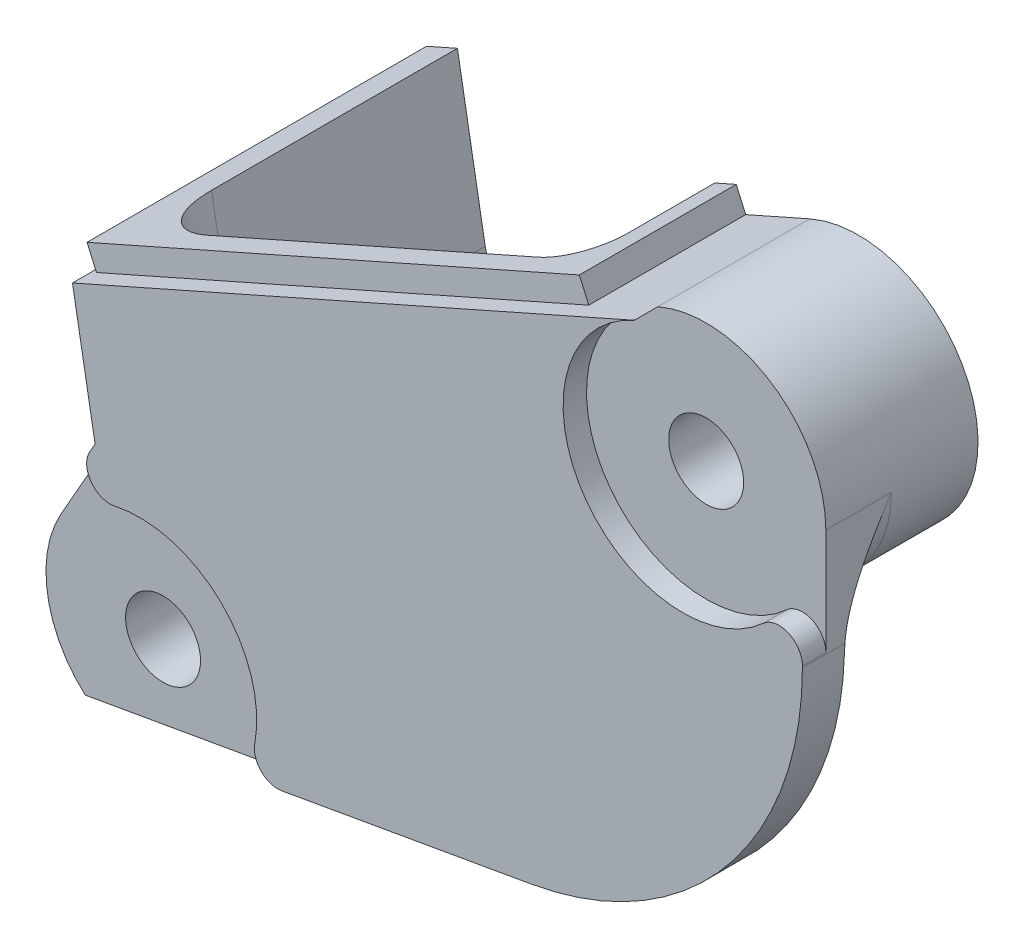
SolidWorks part; units mm, degrees
ref_plane "前视基准面" through (0, 0, 0) normal (0, 0, 1) x (1, 0, 0)
ref_plane "上视基准面" through (0, 0, 0) normal (0, 1, 0) x (1, 0, 0)
ref_plane "右视基准面" through (0, 0, 0) normal (1, 0, 0) x (0, 0, -1)
other "Configuration Table"
sketch "草图1" plane through (0, 0, 0) normal (0, 0, 1) x (1, 0, 0)
  line L0 (-7.0476, 5.9136) -> (0, 5.9136) construction
  line L1 (0, 5.9136) -> (0, 0) construction
  line L2 (0, 0) -> (-7.0476, 5.9136) construction
  line L3 (-12.4776, 6.0041) -> (2.6676, 12.706)
  line L4 (2.6676, 12.706) -> (2.6676, -8.6685)
  line L5 (-12.4776, 6.0041) -> (-12.4776, -11.339)
  line L6 (-12.4776, -11.339) -> (2.6676, -8.6685)
  circle A0 centre (0, 0) radius 1
  circle A1 centre (-7.0476, 5.9136) radius 1
  dimension "D1" = 9.2
  dimension "D3" = 2
  dimension "D4" = 2
  dimension "D9" = 5.43
  dimension "D8" = 9
  dimension "D2" = 50
  dimension "D5" = 2.28
  dimension "D6" = 63.87
  dimension "D7" = 2.6676
  dimension "D10" = 50
extrude "凸台-拉伸1" add sketch "草图1" along normal blind 1.4
sketch "草图2" plane through (0, 0, 0) normal (0, 0, -1) x (-1, 0, 0)
  circle A0 centre (7.0476, 5.9136) radius 2
  circle A1 centre (7.0476, 5.9136) radius 1 construction
  circle A2 centre (7.0476, 5.9136) radius 1
  dimension "D1" = 4
extrude "凸台-拉伸2" add sketch "草图2" along normal blind 1
sketch "草图3" plane through (0, 0, 0) normal (0, 0, -1) x (-1, 0, 0)
  circle A0 centre (0, 0) radius 2
  circle A1 centre (0, 0) radius 1 construction
  circle A2 centre (0, 0) radius 1
  circle A4 centre (7.0476, 5.9136) radius 2 construction
extrude "凸台-拉伸3" add sketch "草图3" along normal blind 0.4
sketch "草图4" plane through (0, 0, 1.4) normal (0, 0, 1) x (1, 0, 0)
  circle A0 centre (-7.0476, 5.9136) radius 1 construction
  circle A1 centre (-7.0476, 5.9136) radius 1
extrude "凸台-拉伸4" add sketch "草图4" against normal blind 1
sketch "草图5" plane through (0, 0, 1.4) normal (0, 0, 1) x (1, 0, 0)
  line L0 (0, 0) -> (8.1261, 1.4328) construction
  line L1 (8.1261, 1.4328) -> (8.1261, 9.5328) construction
  line L2 (-12.4776, -11.339) -> (2.6676, -8.6685) construction
  line L5 (2.6676, 12.706) -> (2.6676, -8.6685)
  line L6 (2.6676, -8.6685) -> (13.2367, -6.8049)
  line L7 (13.2367, -6.8049) -> (13.2367, 9.5328)
  line L8 (-12.4776, -11.339) -> (-14.5289, -11.7007) construction
  line L9 (-14.5289, -11.7007) -> (-15.0672, -8.6478) construction
  line L10 (0, 0) -> (1.5628, -8.8633) construction
  line L11 (-12.4776, -11.339) -> (-18.3923, -12.3819)
  line L12 (-12.4776, 6.0041) -> (-19.4121, -6.1736)
  line L13 (-12.4776, 6.0041) -> (-12.4776, -11.339)
  line L14 (2.6676, 12.706) -> (6.058, 14.2063)
  line L15 (2.6676, 12.706) -> (-12.4776, 6.0041) construction
  line L16 (8.1261, 9.5328) -> (9.5113, 1.6771) construction
  line L17 (9.5113, 1.6771) -> (8.1261, 1.4328) construction
  arc A0 (13.2367, 9.5328) -> (6.058, 14.2063) centre (8.1261, 9.5328) ccw
  arc A4 (-19.4121, -6.1736) -> (-18.3923, -12.3819) centre (-15.0672, -8.6478) ccw
  dimension "D1" = 8.1
  dimension "D2" = 9.658
  dimension "D3" = 16.34
  dimension "D5" = 5
  dimension "D4" = 3.1
extrude "凸台-拉伸5" add sketch "草图5" against normal up to surface (1.4 mm away) up to face at (-5.0476, 5.9136, 0)
sketch "草图6" plane through (0, 0, 1.4) normal (0, 0, 1) x (1, 0, 0)
  line L4 (6.058, 14.2063) -> (-12.4776, 6.0041)
  line L5 (-12.4776, 6.0041) -> (-19.4121, -6.1736)
  line L6 (-18.3923, -12.3819) -> (13.2367, -6.8049)
  line L7 (13.2367, -6.8049) -> (13.2367, 9.5328)
  line L8 (6.058, 14.2063) -> (-12.4776, 6.0041)
  line L9 (-12.4776, 6.0041) -> (-19.4121, -6.1736)
  line L10 (-18.3923, -12.3819) -> (13.2367, -6.8049)
  line L11 (13.2367, -6.8049) -> (13.2367, 9.5328)
  arc A2 (-19.4121, -6.1736) -> (-18.3923, -12.3819) centre (-15.0672, -8.6478) ccw
  arc A3 (13.2367, 9.5328) -> (6.058, 14.2063) centre (8.1261, 9.5328) ccw
  arc A4 (-19.4121, -6.1736) -> (-18.3923, -12.3819) centre (-15.0672, -8.6478) ccw
  arc A5 (13.2367, 9.5328) -> (6.058, 14.2063) centre (8.1261, 9.5328) ccw
  dimension "D1" = 0
extrude "凸台-拉伸6" add sketch "草图6" along normal blind 0.4
sketch "草图7" plane through (0, 0, 0) normal (0, 0, -1) x (-1, 0, 0)
  line L0 (10.6655, -11.0195) -> (18.3923, -12.3819)
  line L1 (18.3923, -12.3819) -> (-13.2367, -6.8049) construction
  circle A0 centre (15.0672, -8.6478) radius 1.6
  arc A1 (18.3923, -12.3819) -> (19.4121, -6.1736) centre (15.0672, -8.6478) ccw construction
  arc A2 (18.3923, -12.3819) -> (10.6655, -11.0195) centre (15.0672, -8.6478) ccw
  dimension "D1" = 3.2
extrude "凸台-拉伸7" add sketch "草图7" along normal blind 8.7
sketch "草图8" plane through (0, 0, 0) normal (0, 0, -1) x (-1, 0, 0)
  circle A0 centre (-8.1261, 9.5328) radius 5.1106
  circle A1 centre (-8.1261, 9.5328) radius 1.6
  circle A2 centre (15.0672, -8.6478) radius 1.6 construction
extrude "凸台-拉伸8" add sketch "草图8" along normal blind 5.7
sketch "草图9" plane through (0, 0, 0) normal (0, 0, -1) x (-1, 0, 0)
  line L0 (10.6655, -11.0195) -> (-0.2432, -9.096)
  line L1 (10.6655, -11.0195) -> (-13.2367, -6.8049) construction
  line L2 (-0.2432, -9.096) -> (-0.0695, -8.1112)
  line L3 (-0.0695, -8.1112) -> (10.2339, -9.9279)
  arc A0 (18.3923, -12.3819) -> (10.6655, -11.0195) centre (15.0672, -8.6478) ccw construction
  arc A1 (10.2339, -9.9279) -> (10.6655, -11.0195) centre (15.0672, -8.6478) ccw
  dimension "D1" = 15
  dimension "D2" = 1
extrude "凸台-拉伸9" add sketch "草图9" along normal up to surface (8.7 mm away) up to face at (-15.2322, -7.7122, -8.7)
sketch "草图10" plane through (-4.265, 9.6382, 0) normal (-0.4047, 0.9145, 0) x (0.9145, 0.4047, 0)
  line L0 (11.2886, 0) -> (11.2886, -1.8) construction
  line L1 (-8.9807, 0) -> (11.2886, 0)
  line L2 (-8.9807, 0) -> (-8.9807, -1)
  line L3 (-8.9807, -1) -> (11.2886, -1)
  line L4 (11.2886, 0) -> (11.2886, -1)
  dimension "D1" = 1
extrude "凸台-拉伸10" add sketch "草图10" along normal blind 1
sketch "草图12" plane through (0, 0, 1.8) normal (0, 0, 1) x (1, 0, 0)
  line L0 (-15.0672, -8.6478) -> (-17.2763, 3.8806) construction
  line L1 (-18.3923, -12.3819) -> (13.2367, -6.8049) construction
  line L2 (6.058, 14.2063) -> (-12.4776, 6.0041) construction
  line L3 (-12.4776, 6.0041) -> (-17.2763, 3.8806)
  line L4 (-17.2763, 3.8806) -> (-16.4276, -0.9325)
  line L5 (-12.4776, 6.0041) -> (-19.4121, -6.1736) construction
  line L6 (-12.4776, 6.0041) -> (-16.4276, -0.9325)
extrude "凸台-拉伸12" add sketch "草图12" against normal up to surface (1.8 mm away) up to face at (2, 0, 0)
sketch "草图11" plane through (0, 0, 0) normal (0, 0, -1) x (-1, 0, 0)
  line L1 (16.6163, -3.8938) -> (15.2376, -3.6507)
  line L2 (16.6163, -3.8938) -> (18.1145, 4.6032)
  line L3 (18.1145, 4.6032) -> (16.7958, 5.1867)
  line L4 (15.2376, -3.6507) -> (16.7958, 5.1867)
  line L5 (10.2339, -9.9279) -> (-0.0695, -8.1112) construction
  line L6 (17.2763, 3.8806) -> (12.4776, 6.0041) construction
  line L7 (-5.6534, 15.1208) -> (12.8823, 6.9185) construction
  arc A1 (19.4121, -6.1736) -> (10.2339, -9.9279) centre (15.0672, -8.6478) ccw construction
  dimension "D1" = 1.4
  dimension "D2" = 90
extrude "凸台-拉伸11" add sketch "草图11" along normal up to surface (8.7 mm away) up to face at (-7.627, -8.0554, -8.7)
sketch "草图13" plane through (0, 0, 0) normal (0, 0, 1) x (1, 0, 0)
  line L6 (-16.4276, -0.9325) -> (-17.2763, 3.8806)
  line L7 (-17.2763, 3.8806) -> (-16.617, 4.1723)
  line L8 (-16.617, 4.1723) -> (-16.7958, 5.1867)
  line L9 (-16.7958, 5.1867) -> (-18.1145, 4.6032)
  line L10 (-18.1145, 4.6032) -> (-16.9704, -1.8856)
  line L11 (-16.9704, -1.8856) -> (-16.4276, -0.9325)
  line L12 (-16.4276, -0.9325) -> (-17.2763, 3.8806)
  line L13 (-17.2763, 3.8806) -> (-16.617, 4.1723)
  line L14 (-16.617, 4.1723) -> (-16.7958, 5.1867)
  line L15 (-16.7958, 5.1867) -> (-18.1145, 4.6032)
  line L16 (-18.1145, 4.6032) -> (-16.9704, -1.8856)
  line L17 (-16.9704, -1.8856) -> (-16.4276, -0.9325)
  dimension "D1" = 0
extrude "凸台-拉伸13" add sketch "草图13" along normal up to surface (1.8 mm away) up to face at (-5.5441, 0.4418, 1.8)
sketch "草图14" plane through (-8.2126, -3.6342, 0) normal (-0.9145, -0.4047, 0) x (0, 0, 1)
  line L4 (0, 10.5397) -> (1, 10.5397)
  line L5 (1, 10.5397) -> (1, 11.5397)
  line L6 (1, 11.5397) -> (0, 11.5397)
  line L7 (0, 11.5397) -> (0, 10.5397)
  line L8 (0, 10.5397) -> (1, 10.5397)
  line L9 (1, 10.5397) -> (1, 11.5397)
  line L10 (1, 11.5397) -> (0, 11.5397)
  line L11 (0, 11.5397) -> (0, 10.5397)
  dimension "D1" = 0
extrude "凸台-拉伸14" add sketch "草图14" along normal up to surface (4.2796 mm away) up to face at (-16.2168, 1.9028, -2.3)
sketch "草图15" plane through (0, 0, 0) normal (0, 0, -1) x (-1, 0, 0)
  line L0 (-2.91, 13.9068) -> (-3.3146, 12.9923)
  line L1 (-5.6534, 15.1208) -> (16.7958, 5.1867) construction
  line L2 (-2.91, 13.9068) -> (-1.9955, 13.5021)
  line L3 (-1.9955, 13.5021) -> (-3.181, 10.823)
  line L4 (-3.3146, 12.9923) -> (-6.058, 14.2063)
  circle A0 centre (-8.1261, 9.5328) radius 5.1106 construction
  circle A1 centre (-8.1261, 9.5328) radius 1.6 construction
  arc A2 (-3.181, 10.823) -> (-3.7084, 12.1024) centre (-8.1261, 9.5328) ccw
  arc A3 (-13.2367, 9.5328) -> (-6.058, 14.2063) centre (-8.1261, 9.5328) ccw construction
  arc A4 (-3.181, 10.823) -> (-6.058, 14.2063) centre (-8.1261, 9.5328) ccw
  line M7 (16.7958, 5.1867) -> (-5.6534, 15.1208)
  arc M9 (-6.058, 14.2063) -> (-13.2367, 9.5328) centre (-8.1261, 9.5328) cw
  dimension "D1" = 3
  dimension "D2" = 1
extrude "凸台-拉伸15" add sketch "草图15" along normal up to surface (5.7 mm away) contours L0 L4 L3 M9 M7 region at (3.2475, 12.702, 0) up to face at (3.0155, 9.5328, -5.7)
sketch "草图16" plane through (0, 0, -8.7) normal (0, 0, -1) x (-1, 0, 0)
  line L0 (15.3649, -2.9284) -> (16.6836, -3.5119)
  line L6 (16.6163, -3.8938) -> (18.1145, 4.6032)
  line L7 (18.1145, 4.6032) -> (16.7958, 5.1867)
  line L8 (16.7958, 5.1867) -> (15.2376, -3.6507)
  line L9 (10.2339, -9.9279) -> (-0.0695, -8.1112)
  line L10 (-0.0695, -8.1112) -> (-0.2432, -9.096)
  line L11 (-0.2432, -9.096) -> (18.3923, -12.3819)
  line L12 (16.6836, -3.5119) -> (18.1145, 4.6032)
  line L13 (18.1145, 4.6032) -> (16.7958, 5.1867)
  line L14 (16.7958, 5.1867) -> (15.3649, -2.9284)
  arc A2 (18.3923, -12.3819) -> (16.6163, -3.8938) centre (15.0672, -8.6478) ccw
  arc A3 (15.2376, -3.6507) -> (10.2339, -9.9279) centre (15.0672, -8.6478) ccw
  line M11 (16.6163, -3.8938) -> (18.1145, 4.6032)
  line M12 (18.1145, 4.6032) -> (16.7958, 5.1867)
  line M13 (16.7958, 5.1867) -> (15.2376, -3.6507)
  dimension "D2" = 8
  dimension "D1" = 0
extrude "凸台-拉伸16" add sketch "草图16" along normal blind 4.8 contours L0 M13 M11 M12 region at (-16.7397, 0.8374, -8.7)
fillet "圆角1" radius 14 1 edges at (13.2367, -6.8049, 0.9)
fillet "圆角3" radius 2 2 edges at (7.4757, 4.4638, 0) (2.5883, 12.1626, 0)
sketch "草图17" plane through (0, 0, 0) normal (0, 0, -1) x (-1, 0, 0)
  circle A1 centre (15.0672, -8.6478) radius 1.6
  circle A2 centre (15.0672, -8.6478) radius 1.6
  circle A3 centre (-8.1261, 9.5328) radius 1.6
  circle A4 centre (-8.1261, 9.5328) radius 1.6
  dimension "D1" = 0
  dimension "D2" = 0
extrude "切除-拉伸1" cut sketch "草图17" against normal through all
sketch "草图18" plane through (0, 0, 1.8) normal (0, 0, 1) x (1, 0, 0)
  circle A0 centre (-15.0672, -8.6478) radius 5
  circle A1 centre (8.1261, 9.5328) radius 5.1106
extrude "切除-拉伸2" cut sketch "草图18" against normal blind 1
fillet "圆角4" radius 1 3 edges at (13.2367, 9.5328, 1.3) (-19.4121, -6.1736, 1.3) (-10.6655, -11.0195, 1.3)
sketch "草图19" plane through (0, 0, -8.7) normal (0, 0, -1) x (-1, 0, 0)
  line L0 (-0.2432, -9.096) -> (18.3923, -12.3819) construction
  line L1 (-0.0695, -8.1112) -> (-0.2432, -9.096) construction
  line L2 (10.2339, -9.9279) -> (-0.0695, -8.1112) construction
  line L3 (-0.2432, -9.096) -> (10.6655, -11.0195)
  line L4 (-0.0695, -8.1112) -> (-0.2432, -9.096)
  line L5 (10.2339, -9.9279) -> (-0.0695, -8.1112)
  arc A0 (10.2339, -9.9279) -> (10.6655, -11.0195) centre (15.0672, -8.6478) ccw
extrude "切除-拉伸3" cut sketch "草图19" against normal up to surface (8.7 mm away) up to face at (-5.0476, 5.9136, 0)
fillet "圆角2" radius 3 3 edges at (-15.2376, -3.6507, -4.35) (-16.0167, 0.768, 0) (-10.8186, -6.0117, 0)
sketch "草图20" plane through (-15.4024, -2.7159, 0) normal (0.9848, 0.1736, 0) x (0, 0, -1)
  line L4 (-1, 6.9945) -> (-1, 8.0245)
  line L5 (-1, 8.0245) -> (-1.8, 8.0245)
  line L6 (-1.8, 8.0245) -> (-1.8, 6.9945)
  line L7 (-1.8, 6.9945) -> (-1, 6.9945)
  line L8 (-1, 6.9945) -> (-1, 8.0245)
  line L9 (-1, 8.0245) -> (-1.8, 8.0245)
  line L10 (-1.8, 8.0245) -> (-1.8, 6.9945)
  line L11 (-1.8, 6.9945) -> (-1, 6.9945)
  dimension "D1" = 0
extrude "切除-拉伸4" cut sketch "草图20" along direction (0.9145, 0.4047, 0) on the side against the normal up to next (1.4 mm away)
sketch "草图21" plane through (0, 0, 1) normal (0, 0, 1) x (1, 0, 0)
  line L0 (-18.1145, 4.6032) -> (-17.7099, 3.6887)
  line L1 (6.058, 14.2063) -> (-17.9357, 3.5888) construction
  line L2 (-17.7099, 3.6887) -> (-17.9357, 3.5888)
  line L3 (-17.9357, 3.5888) -> (-18.1145, 4.6032)
  line L4 (5.6534, 15.1208) -> (6.058, 14.2063) construction
extrude "切除-拉伸5" cut sketch "草图21" against normal up to next
sketch "草图22" plane through (0, 0, 0) normal (0, 0, -1) x (-1, 0, 0)
  line L4 (-3.3146, 12.9923) -> (-2.91, 13.9068)
  line L5 (-2.91, 13.9068) -> (-5.6534, 15.1208)
  line L6 (-5.6534, 15.1208) -> (-6.058, 14.2063)
  line L7 (-6.058, 14.2063) -> (-3.3146, 12.9923)
  line L8 (-3.3146, 12.9923) -> (-2.91, 13.9068)
  line L9 (-2.91, 13.9068) -> (-5.6534, 15.1208)
  line L10 (-5.6534, 15.1208) -> (-6.058, 14.2063)
  line L11 (-6.058, 14.2063) -> (-3.3146, 12.9923)
  dimension "D1" = 0
extrude "切除-拉伸6" cut sketch "草图22" against normal up to next
